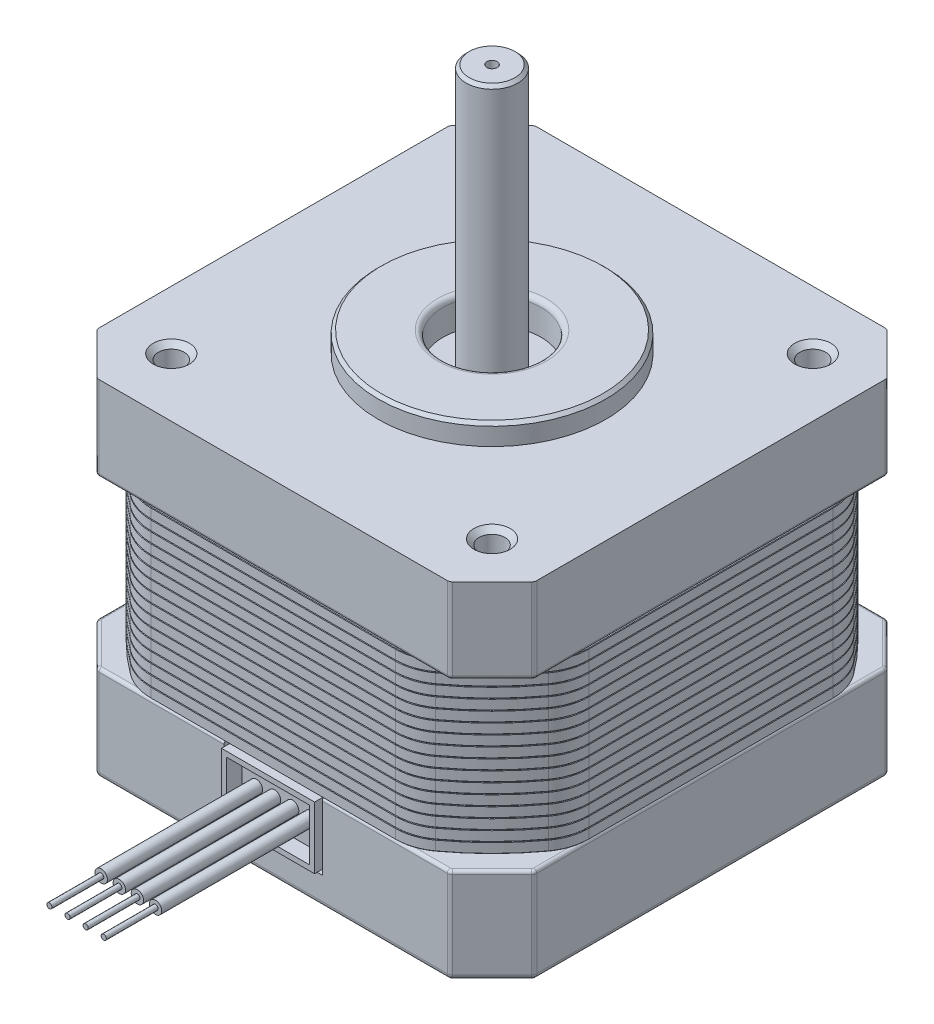
SolidWorks part; units mm, degrees
note: The reader was unsure of these and kept them because the rebuilt part matched: shared geometry of "Эскиз1<3>", "Эскиз12<2>".
ref_plane "Спереди" through (0, 0, 0) normal (0, 0, 1) x (1, 0, 0)
ref_plane "Сверху" through (0, 0, 0) normal (0, 1, 0) x (1, 0, 0)
ref_plane "Справа" through (0, 0, 0) normal (1, 0, 0) x (0, 0, -1)
sketch "Эскиз1" plane through (0, 0, 0) normal (0, 1, 0) x (1, 0, 0)
  line L0 (-21.15, 17.0338) -> (-17.0338, 21.15)
  line L1 (-21.15, 21.15) -> (21.15, 21.15)
  line L2 (-21.15, 21.15) -> (-21.15, -21.15)
  line L3 (-21.15, -21.15) -> (21.15, -21.15)
  line L4 (21.15, 21.15) -> (21.15, -21.15)
  line L5 (-21.15, 21.15) -> (21.15, -21.15) construction
  line L6 (-21.15, -21.15) -> (21.15, 21.15) construction
  line L7 (-17.0338, 21.15) -> (17.0338, 21.15)
  line L8 (17.0338, 21.15) -> (21.15, 17.0338)
  line L9 (21.15, 17.0338) -> (21.15, -17.0338)
  line L10 (21.15, -17.0338) -> (17.0338, -21.15)
  line L11 (17.0338, -21.15) -> (-17.0338, -21.15)
  line L12 (-17.0338, -21.15) -> (-21.15, -17.0338)
  point P0 (0, 0)
  dimension "D1" = 42.3
  dimension "D2" = 54
extrude "Бобышка-Вытянуть1" add sketch "Эскиз1" along normal blind 9.2 contours L12 L3 L10 L4 L8 L1 L0 L2
extrude "Бобышка-Вытянуть2" add sketch "Эскиз1<3>" against normal blind 8.2 from offset 33.4 separate body contours L12 L3 L10 L4 L8 L1 L0 L2
sketch "Эскиз1<3>" plane through (0, 0, 0) normal (0, 1, 0) x (1, 0, 0) same geometry as "Эскиз1"
sketch "Эскиз2" plane through (0, 9.2, 0) normal (0, 1, 0) x (1, 0, 0)
  line L16 (-21.15, -17.0338) -> (-17.0338, -21.15)
  line L17 (-17.0338, -21.15) -> (17.0338, -21.15)
  line L18 (17.0338, -21.15) -> (21.15, -17.0338)
  line L19 (21.15, -17.0338) -> (21.15, 17.0338)
  line L20 (21.15, 17.0338) -> (17.0338, 21.15)
  line L21 (17.0338, 21.15) -> (-17.0338, 21.15)
  line L22 (-17.0338, 21.15) -> (-21.15, 17.0338)
  line L23 (-21.15, 17.0338) -> (-21.15, -17.0338)
  line L25 (-11.7974, -21.15) -> (11.7974, -21.15)
  line L27 (21.15, -11.7974) -> (21.15, 11.7974)
  line L29 (11.7974, 21.15) -> (-11.7974, 21.15)
  line L31 (-21.15, 11.7974) -> (-21.15, -11.7974)
  arc A0 (-20.1875, -14.7467) -> (-14.7467, -20.1875) centre (0, 0) ccw
  arc A1 (-14.7467, 20.1875) -> (-20.1875, 14.7467) centre (0, 0) ccw
  arc A2 (20.1875, 14.7467) -> (14.7467, 20.1875) centre (0, 0) ccw
  arc A3 (14.7467, -20.1875) -> (20.1875, -14.7467) centre (0, 0) ccw
  arc A4 (14.7467, 20.1875) -> (11.7974, 21.15) centre (11.7974, 16.15) ccw
  arc A5 (21.15, 11.7974) -> (20.1875, 14.7467) centre (16.15, 11.7974) ccw
  arc A6 (20.1875, -14.7467) -> (21.15, -11.7974) centre (16.15, -11.7974) ccw
  arc A7 (11.7974, -21.15) -> (14.7467, -20.1875) centre (11.7974, -16.15) ccw
  arc A8 (-14.7467, -20.1875) -> (-11.7974, -21.15) centre (-11.7974, -16.15) ccw
  arc A9 (-20.1875, -14.7467) -> (-21.15, -11.7974) centre (-16.15, -11.7974) cw
  arc A10 (-20.1875, 14.7467) -> (-21.15, 11.7974) centre (-16.15, 11.7974) ccw
  arc A11 (-11.7974, 21.15) -> (-14.7467, 20.1875) centre (-11.7974, 16.15) ccw
  point P22 (21.15, 13.3296)
  point P27 (13.3296, -21.15)
  point P36 (-13.3296, 21.15)
  dimension "D1" = 50
  dimension "D3" = 5
  dimension "D2" = 0
extrude "Бобышка-Вытянуть3" add sketch "Эскиз2" along normal blind 1 separate body
pattern_linear "Линейный массив1" count 16 spacing 1 along (0, 1, 0) of bodies 105
sketch "Эскиз3" plane through (0, 0, 0) normal (0, -1, 0) x (1, 0, 0)
  circle A0 centre (0, 0) radius 4.75
  dimension "D1" = 9.5
extrude "Вырез-Вытянуть1" cut sketch "Эскиз3" against normal blind 3
sketch "Эскиз4" plane through (0, 3, 0) normal (0, -1, 0) x (1, 0, 0)
  circle A0 centre (0, 0) radius 2.5
  circle A1 centre (0, 0) radius 4.75
  dimension "D1" = 5
extrude "Вырез-Вытянуть2" cut sketch "Эскиз4" against normal blind 0.5
sketch "Эскиз5" plane through (0, 3, 0) normal (0, -1, 0) x (1, 0, 0)
  circle A0 centre (0, 0) radius 0.5
  dimension "D1" = 1
extrude "Вырез-Вытянуть3" cut sketch "Эскиз5" against normal blind 0.5
chamfer "Фаска1" distance 0.3 angle 45 1 edges at (0, 3, -2.5)
fillet "Скругление1" radius 0.5 17 edges at (0, 0, 21.15) (19.0919, 0, 19.0919) (21.15, 0, 0) (19.0919, 0, -19.0919) (0, 0, -21.15) (-19.0919, 0, -19.0919) (-21.15, 0, 0) (-19.0919, 0, 19.0919) (0, 0, -4.75) (21.15, 4.6, 17.0338) (17.0338, 4.6, 21.15) (-17.0338, 4.6, 21.15) (-21.15, 4.6, 17.0338) (-21.15, 4.6, -17.0338) (-17.0338, 4.6, -21.15) (17.0338, 4.6, -21.15) (21.15, 4.6, -17.0338)
fillet "Скругление2" radius 0.5 8 edges at (21.15, 29.3, 17.0338) (17.0338, 29.3, 21.15) (-17.0338, 29.3, 21.15) (-21.15, 29.3, 17.0338) (-21.15, 29.3, -17.0338) (-17.0338, 29.3, -21.15) (17.0338, 29.3, -21.15) (21.15, 29.3, -17.0338)
sketch "Эскиз6" plane through (0, 33.4, 0) normal (0, 1, 0) x (1, 0, 0)
  circle A0 centre (0, 0) radius 11
  circle A1 centre (0, 0) radius 4.75
  dimension "D1" = 22
  dimension "D2" = 9.5
extrude "Бобышка-Вытянуть4" add sketch "Эскиз6" along normal blind 2
sketch "Эскиз7" plane through (0, 33.4, 0) normal (0, 1, 0) x (1, 0, 0)
  circle A2 centre (0, 0) radius 4.75
  circle A3 centre (0, 0) radius 4.75
  dimension "D1" = 0
extrude "Вырез-Вытянуть4" cut sketch "Эскиз7" against normal blind 1
chamfer "Фаска2" distance 0.3 angle 45 1 edges at (0, 35.4, 11)
fillet "Скругление3" radius 0.5 1 edges at (0, 35.4, 4.75)
sketch "Эскиз8" plane through (0, 32.4, 0) normal (0, 1, 0) x (1, 0, 0)
  circle A0 centre (0, 0) radius 2.5
  dimension "D1" = 5
extrude "Бобышка-Вытянуть5" add sketch "Эскиз8" along normal blind 25.2
chamfer "Фаска4" distance 0.3 angle 45 1 edges at (0, 57.6, 2.5)
sketch "Эскиз9" plane through (0, 57.6, 0) normal (0, 1, 0) x (1, 0, 0)
  circle A0 centre (0, 0) radius 0.5
  dimension "D1" = 1
extrude "Вырез-Вытянуть5" cut sketch "Эскиз9" against normal blind 1
sketch "Эскиз10" plane through (0, 0, 21.15) normal (0, 0, 1) x (1, 0, 0)
  line L0 (0, 0) -> (0, 9.2) construction
  line L1 (-11.7974, 9.2) -> (11.7974, 9.2) construction
  line L2 (-16.8267, 9.2) -> (16.8267, 9.2) construction
  line L3 (-4.75, 2.7) -> (4.75, 2.7)
  line L4 (-4.75, 2.7) -> (-4.75, 9.2)
  line L5 (-4.75, 9.2) -> (4.75, 9.2)
  line L6 (4.75, 2.7) -> (4.75, 9.2)
  line L7 (-4.75, 2.7) -> (4.75, 9.2) construction
  line L8 (-4.75, 9.2) -> (4.75, 2.7) construction
  point P5 (0, 5.95)
  dimension "D1" = 9.5
  dimension "D2" = 6.5
extrude "Вырез-Вытянуть6" cut sketch "Эскиз10" against normal blind 1
sketch "Эскиз11" plane through (0, 0, 20.15) normal (0, 0, 1) x (1, 0, 0)
  line L8 (4.5, 2.95) -> (4.5, 8.95)
  line L9 (4.5, 8.95) -> (-4.5, 8.95)
  line L10 (-4.5, 8.95) -> (-4.5, 2.95)
  line L11 (-4.5, 2.95) -> (4.5, 2.95)
  line L12 (4.5, 2.95) -> (4.5, 8.95)
  line L13 (4.5, 8.95) -> (-4.5, 8.95)
  line L14 (-4.5, 8.95) -> (-4.5, 2.95)
  line L15 (-4.5, 2.95) -> (4.5, 2.95)
  line L20 (4, 3.45) -> (4, 8.45)
  line L21 (4, 8.45) -> (-4, 8.45)
  line L22 (-4, 8.45) -> (-4, 3.45)
  line L23 (-4, 3.45) -> (4, 3.45)
  line L24 (4, 3.45) -> (4, 8.45)
  line L25 (4, 8.45) -> (-4, 8.45)
  line L26 (-4, 8.45) -> (-4, 3.45)
  line L27 (-4, 3.45) -> (4, 3.45)
  dimension "D1" = 0.25
  dimension "D2" = 0.75
extrude "Бобышка-Вытянуть6" add sketch "Эскиз11" along normal blind 1.5 separate body
sketch "Эскиз12" plane through (0, 0, 20.15) normal (0, 0, 1) x (1, 0, 0)
  line L0 (-4, 5.95) -> (4, 5.95) construction
  line L1 (-4, 8.45) -> (-4, 3.45) construction
  line L2 (4, 3.45) -> (4, 8.45) construction
  line L3 (-2.625, 5.95) -> (-2.625, 4.3362) construction
  line L4 (-2.625, 4.3362) -> (-0.875, 4.3362) construction
  line L5 (-0.875, 4.3362) -> (-0.875, 5.95) construction
  line L6 (-0.875, 5.95) -> (-0.875, 4.3362) construction
  line L7 (-0.875, 4.3362) -> (0.875, 4.3362) construction
  line L8 (0.875, 4.3362) -> (0.875, 5.95) construction
  line L9 (0.875, 5.95) -> (0.875, 4.3362) construction
  line L10 (0.875, 4.3362) -> (2.625, 4.3362) construction
  line L11 (2.625, 4.3362) -> (2.625, 5.95) construction
  line L12 (0, 5.95) -> (0, 4.3362) construction
  circle A0 centre (-2.625, 5.95) radius 0.6
  circle A1 centre (-0.875, 5.95) radius 0.6
  circle A2 centre (0.875, 5.95) radius 0.6
  circle A3 centre (2.625, 5.95) radius 0.6
  circle A4 centre (-2.625, 5.95) radius 0.25
  circle A5 centre (-0.875, 5.95) radius 0.25
  circle A6 centre (0.875, 5.95) radius 0.25
  circle A7 centre (2.625, 5.95) radius 0.25
  dimension "D1" = 1.2
  dimension "D2" = 0.5
  dimension "D3" = 1.75
extrude "Бобышка-Вытянуть7" add sketch "Эскиз12" along normal blind 15 separate body
extrude "Бобышка-Вытянуть8" add sketch "Эскиз12<2>" along normal blind 20 separate body contours A4 | A5 | A6 | A7
sketch "Эскиз12<2>" plane through (0, 0, 20.15) normal (0, 0, 1) x (1, 0, 0) same geometry as "Эскиз12"
chamfer "Фаска19" distance 0.05 angle 45 32 edges at (-17.6777, 25.2, -17.6777) (-20.9033, 25.2, -13.3486) (-13.3486, 25.2, -20.9033) (-21.15, 25.2, 0) (0, 25.2, -21.15) (-20.9033, 25.2, 13.3486) (13.3486, 25.2, -20.9033) (-17.6777, 25.2, 17.6777) (17.6777, 25.2, -17.6777) (-13.3486, 25.2, 20.9033) (20.9033, 25.2, -13.3486) (0, 25.2, 21.15) (21.15, 25.2, 0) (13.3486, 25.2, 20.9033) (20.9033, 25.2, 13.3486) (17.6777, 25.2, 17.6777) (-17.6777, 24.2, -17.6777) (-20.9033, 24.2, -13.3486) (-13.3486, 24.2, -20.9033) (-21.15, 24.2, 0) (0, 24.2, -21.15) (-20.9033, 24.2, 13.3486) (13.3486, 24.2, -20.9033) (-17.6777, 24.2, 17.6777) (17.6777, 24.2, -17.6777) (-13.3486, 24.2, 20.9033) (20.9033, 24.2, -13.3486) (0, 24.2, 21.15) (21.15, 24.2, 0) (13.3486, 24.2, 20.9033) (20.9033, 24.2, 13.3486) (17.6777, 24.2, 17.6777)
chamfer "Фаска20" distance 0.05 angle 45 32 edges at (-17.6777, 24.2, -17.6777) (-20.9033, 24.2, -13.3486) (-13.3486, 24.2, -20.9033) (-21.15, 24.2, 0) (0, 24.2, -21.15) (-20.9033, 24.2, 13.3486) (13.3486, 24.2, -20.9033) (-17.6777, 24.2, 17.6777) (17.6777, 24.2, -17.6777) (-13.3486, 24.2, 20.9033) (20.9033, 24.2, -13.3486) (0, 24.2, 21.15) (21.15, 24.2, 0) (13.3486, 24.2, 20.9033) (20.9033, 24.2, 13.3486) (17.6777, 24.2, 17.6777) (-17.6777, 23.2, -17.6777) (-20.9033, 23.2, -13.3486) (-13.3486, 23.2, -20.9033) (-21.15, 23.2, 0) (0, 23.2, -21.15) (-20.9033, 23.2, 13.3486) (13.3486, 23.2, -20.9033) (-17.6777, 23.2, 17.6777) (17.6777, 23.2, -17.6777) (-13.3486, 23.2, 20.9033) (20.9033, 23.2, -13.3486) (0, 23.2, 21.15) (21.15, 23.2, 0) (13.3486, 23.2, 20.9033) (20.9033, 23.2, 13.3486) (17.6777, 23.2, 17.6777)
chamfer "Фаска21" distance 0.05 angle 45 32 edges at (-17.6777, 23.2, -17.6777) (-20.9033, 23.2, -13.3486) (-13.3486, 23.2, -20.9033) (-21.15, 23.2, 0) (0, 23.2, -21.15) (-20.9033, 23.2, 13.3486) (13.3486, 23.2, -20.9033) (-17.6777, 23.2, 17.6777) (17.6777, 23.2, -17.6777) (-13.3486, 23.2, 20.9033) (20.9033, 23.2, -13.3486) (0, 23.2, 21.15) (21.15, 23.2, 0) (13.3486, 23.2, 20.9033) (20.9033, 23.2, 13.3486) (17.6777, 23.2, 17.6777) (-17.6777, 22.2, -17.6777) (-20.9033, 22.2, -13.3486) (-13.3486, 22.2, -20.9033) (-21.15, 22.2, 0) (0, 22.2, -21.15) (-20.9033, 22.2, 13.3486) (13.3486, 22.2, -20.9033) (-17.6777, 22.2, 17.6777) (17.6777, 22.2, -17.6777) (-13.3486, 22.2, 20.9033) (20.9033, 22.2, -13.3486) (0, 22.2, 21.15) (21.15, 22.2, 0) (13.3486, 22.2, 20.9033) (20.9033, 22.2, 13.3486) (17.6777, 22.2, 17.6777)
chamfer "Фаска22" distance 0.05 angle 45 32 edges at (-17.6777, 22.2, -17.6777) (-20.9033, 22.2, -13.3486) (-13.3486, 22.2, -20.9033) (-21.15, 22.2, 0) (0, 22.2, -21.15) (-20.9033, 22.2, 13.3486) (13.3486, 22.2, -20.9033) (-17.6777, 22.2, 17.6777) (17.6777, 22.2, -17.6777) (-13.3486, 22.2, 20.9033) (20.9033, 22.2, -13.3486) (0, 22.2, 21.15) (21.15, 22.2, 0) (13.3486, 22.2, 20.9033) (20.9033, 22.2, 13.3486) (17.6777, 22.2, 17.6777) (-17.6777, 21.2, -17.6777) (-20.9033, 21.2, -13.3486) (-13.3486, 21.2, -20.9033) (-21.15, 21.2, 0) (0, 21.2, -21.15) (-20.9033, 21.2, 13.3486) (13.3486, 21.2, -20.9033) (-17.6777, 21.2, 17.6777) (17.6777, 21.2, -17.6777) (-13.3486, 21.2, 20.9033) (20.9033, 21.2, -13.3486) (0, 21.2, 21.15) (21.15, 21.2, 0) (13.3486, 21.2, 20.9033) (20.9033, 21.2, 13.3486) (17.6777, 21.2, 17.6777)
chamfer "Фаска23" distance 0.05 angle 45 32 edges at (-17.6777, 21.2, -17.6777) (-20.9033, 21.2, -13.3486) (-13.3486, 21.2, -20.9033) (-21.15, 21.2, 0) (0, 21.2, -21.15) (-20.9033, 21.2, 13.3486) (13.3486, 21.2, -20.9033) (-17.6777, 21.2, 17.6777) (17.6777, 21.2, -17.6777) (-13.3486, 21.2, 20.9033) (20.9033, 21.2, -13.3486) (0, 21.2, 21.15) (21.15, 21.2, 0) (13.3486, 21.2, 20.9033) (20.9033, 21.2, 13.3486) (17.6777, 21.2, 17.6777) (-17.6777, 20.2, -17.6777) (-20.9033, 20.2, -13.3486) (-13.3486, 20.2, -20.9033) (-21.15, 20.2, 0) (0, 20.2, -21.15) (-20.9033, 20.2, 13.3486) (13.3486, 20.2, -20.9033) (-17.6777, 20.2, 17.6777) (17.6777, 20.2, -17.6777) (-13.3486, 20.2, 20.9033) (20.9033, 20.2, -13.3486) (0, 20.2, 21.15) (21.15, 20.2, 0) (13.3486, 20.2, 20.9033) (20.9033, 20.2, 13.3486) (17.6777, 20.2, 17.6777)
chamfer "Фаска24" distance 0.05 angle 45 32 edges at (-17.6777, 20.2, -17.6777) (-20.9033, 20.2, -13.3486) (-13.3486, 20.2, -20.9033) (-21.15, 20.2, 0) (0, 20.2, -21.15) (-20.9033, 20.2, 13.3486) (13.3486, 20.2, -20.9033) (-17.6777, 20.2, 17.6777) (17.6777, 20.2, -17.6777) (-13.3486, 20.2, 20.9033) (20.9033, 20.2, -13.3486) (0, 20.2, 21.15) (21.15, 20.2, 0) (13.3486, 20.2, 20.9033) (20.9033, 20.2, 13.3486) (17.6777, 20.2, 17.6777) (-17.6777, 19.2, -17.6777) (-20.9033, 19.2, -13.3486) (-13.3486, 19.2, -20.9033) (-21.15, 19.2, 0) (0, 19.2, -21.15) (-20.9033, 19.2, 13.3486) (13.3486, 19.2, -20.9033) (-17.6777, 19.2, 17.6777) (17.6777, 19.2, -17.6777) (-13.3486, 19.2, 20.9033) (20.9033, 19.2, -13.3486) (0, 19.2, 21.15) (21.15, 19.2, 0) (13.3486, 19.2, 20.9033) (20.9033, 19.2, 13.3486) (17.6777, 19.2, 17.6777)
chamfer "Фаска25" distance 0.05 angle 45 32 edges at (-17.6777, 19.2, -17.6777) (-20.9033, 19.2, -13.3486) (-13.3486, 19.2, -20.9033) (-21.15, 19.2, 0) (0, 19.2, -21.15) (-20.9033, 19.2, 13.3486) (13.3486, 19.2, -20.9033) (-17.6777, 19.2, 17.6777) (17.6777, 19.2, -17.6777) (-13.3486, 19.2, 20.9033) (20.9033, 19.2, -13.3486) (0, 19.2, 21.15) (21.15, 19.2, 0) (13.3486, 19.2, 20.9033) (20.9033, 19.2, 13.3486) (17.6777, 19.2, 17.6777) (-17.6777, 18.2, -17.6777) (-20.9033, 18.2, -13.3486) (-13.3486, 18.2, -20.9033) (-21.15, 18.2, 0) (0, 18.2, -21.15) (-20.9033, 18.2, 13.3486) (13.3486, 18.2, -20.9033) (-17.6777, 18.2, 17.6777) (17.6777, 18.2, -17.6777) (-13.3486, 18.2, 20.9033) (20.9033, 18.2, -13.3486) (0, 18.2, 21.15) (21.15, 18.2, 0) (13.3486, 18.2, 20.9033) (20.9033, 18.2, 13.3486) (17.6777, 18.2, 17.6777)
chamfer "Фаска26" distance 0.05 angle 45 32 edges at (-17.6777, 18.2, -17.6777) (-20.9033, 18.2, -13.3486) (-13.3486, 18.2, -20.9033) (-21.15, 18.2, 0) (0, 18.2, -21.15) (-20.9033, 18.2, 13.3486) (13.3486, 18.2, -20.9033) (-17.6777, 18.2, 17.6777) (17.6777, 18.2, -17.6777) (-13.3486, 18.2, 20.9033) (20.9033, 18.2, -13.3486) (0, 18.2, 21.15) (21.15, 18.2, 0) (13.3486, 18.2, 20.9033) (20.9033, 18.2, 13.3486) (17.6777, 18.2, 17.6777) (-17.6777, 17.2, -17.6777) (-20.9033, 17.2, -13.3486) (-13.3486, 17.2, -20.9033) (-21.15, 17.2, 0) (0, 17.2, -21.15) (-20.9033, 17.2, 13.3486) (13.3486, 17.2, -20.9033) (-17.6777, 17.2, 17.6777) (17.6777, 17.2, -17.6777) (-13.3486, 17.2, 20.9033) (20.9033, 17.2, -13.3486) (0, 17.2, 21.15) (21.15, 17.2, 0) (13.3486, 17.2, 20.9033) (20.9033, 17.2, 13.3486) (17.6777, 17.2, 17.6777)
chamfer "Фаска27" distance 0.05 angle 45 32 edges at (-17.6777, 17.2, -17.6777) (-20.9033, 17.2, -13.3486) (-13.3486, 17.2, -20.9033) (-21.15, 17.2, 0) (0, 17.2, -21.15) (-20.9033, 17.2, 13.3486) (13.3486, 17.2, -20.9033) (-17.6777, 17.2, 17.6777) (17.6777, 17.2, -17.6777) (-13.3486, 17.2, 20.9033) (20.9033, 17.2, -13.3486) (0, 17.2, 21.15) (21.15, 17.2, 0) (13.3486, 17.2, 20.9033) (20.9033, 17.2, 13.3486) (17.6777, 17.2, 17.6777) (-17.6777, 16.2, -17.6777) (-20.9033, 16.2, -13.3486) (-13.3486, 16.2, -20.9033) (-21.15, 16.2, 0) (0, 16.2, -21.15) (-20.9033, 16.2, 13.3486) (13.3486, 16.2, -20.9033) (-17.6777, 16.2, 17.6777) (17.6777, 16.2, -17.6777) (-13.3486, 16.2, 20.9033) (20.9033, 16.2, -13.3486) (0, 16.2, 21.15) (21.15, 16.2, 0) (13.3486, 16.2, 20.9033) (20.9033, 16.2, 13.3486) (17.6777, 16.2, 17.6777)
chamfer "Фаска28" distance 0.05 angle 45 32 edges at (-17.6777, 16.2, -17.6777) (-20.9033, 16.2, -13.3486) (-13.3486, 16.2, -20.9033) (-21.15, 16.2, 0) (0, 16.2, -21.15) (-20.9033, 16.2, 13.3486) (13.3486, 16.2, -20.9033) (-17.6777, 16.2, 17.6777) (17.6777, 16.2, -17.6777) (-13.3486, 16.2, 20.9033) (20.9033, 16.2, -13.3486) (0, 16.2, 21.15) (21.15, 16.2, 0) (13.3486, 16.2, 20.9033) (20.9033, 16.2, 13.3486) (17.6777, 16.2, 17.6777) (-17.6777, 15.2, -17.6777) (-20.9033, 15.2, -13.3486) (-13.3486, 15.2, -20.9033) (-21.15, 15.2, 0) (0, 15.2, -21.15) (-20.9033, 15.2, 13.3486) (13.3486, 15.2, -20.9033) (-17.6777, 15.2, 17.6777) (17.6777, 15.2, -17.6777) (-13.3486, 15.2, 20.9033) (20.9033, 15.2, -13.3486) (0, 15.2, 21.15) (21.15, 15.2, 0) (13.3486, 15.2, 20.9033) (20.9033, 15.2, 13.3486) (17.6777, 15.2, 17.6777)
chamfer "Фаска29" distance 0.05 angle 45 32 edges at (-17.6777, 15.2, -17.6777) (-20.9033, 15.2, -13.3486) (-13.3486, 15.2, -20.9033) (-21.15, 15.2, 0) (0, 15.2, -21.15) (-20.9033, 15.2, 13.3486) (13.3486, 15.2, -20.9033) (-17.6777, 15.2, 17.6777) (17.6777, 15.2, -17.6777) (-13.3486, 15.2, 20.9033) (20.9033, 15.2, -13.3486) (0, 15.2, 21.15) (21.15, 15.2, 0) (13.3486, 15.2, 20.9033) (20.9033, 15.2, 13.3486) (17.6777, 15.2, 17.6777) (-17.6777, 14.2, -17.6777) (-20.9033, 14.2, -13.3486) (-13.3486, 14.2, -20.9033) (-21.15, 14.2, 0) (0, 14.2, -21.15) (-20.9033, 14.2, 13.3486) (13.3486, 14.2, -20.9033) (-17.6777, 14.2, 17.6777) (17.6777, 14.2, -17.6777) (-13.3486, 14.2, 20.9033) (20.9033, 14.2, -13.3486) (0, 14.2, 21.15) (21.15, 14.2, 0) (13.3486, 14.2, 20.9033) (20.9033, 14.2, 13.3486) (17.6777, 14.2, 17.6777)
chamfer "Фаска30" distance 0.05 angle 45 32 edges at (-17.6777, 14.2, -17.6777) (-20.9033, 14.2, -13.3486) (-13.3486, 14.2, -20.9033) (-21.15, 14.2, 0) (0, 14.2, -21.15) (-20.9033, 14.2, 13.3486) (13.3486, 14.2, -20.9033) (-17.6777, 14.2, 17.6777) (17.6777, 14.2, -17.6777) (-13.3486, 14.2, 20.9033) (20.9033, 14.2, -13.3486) (0, 14.2, 21.15) (21.15, 14.2, 0) (13.3486, 14.2, 20.9033) (20.9033, 14.2, 13.3486) (17.6777, 14.2, 17.6777) (-17.6777, 13.2, -17.6777) (-20.9033, 13.2, -13.3486) (-13.3486, 13.2, -20.9033) (-21.15, 13.2, 0) (0, 13.2, -21.15) (-20.9033, 13.2, 13.3486) (13.3486, 13.2, -20.9033) (-17.6777, 13.2, 17.6777) (17.6777, 13.2, -17.6777) (-13.3486, 13.2, 20.9033) (20.9033, 13.2, -13.3486) (0, 13.2, 21.15) (21.15, 13.2, 0) (13.3486, 13.2, 20.9033) (20.9033, 13.2, 13.3486) (17.6777, 13.2, 17.6777)
chamfer "Фаска31" distance 0.05 angle 45 32 edges at (-17.6777, 13.2, -17.6777) (-20.9033, 13.2, -13.3486) (-13.3486, 13.2, -20.9033) (-21.15, 13.2, 0) (0, 13.2, -21.15) (-20.9033, 13.2, 13.3486) (13.3486, 13.2, -20.9033) (-17.6777, 13.2, 17.6777) (17.6777, 13.2, -17.6777) (-13.3486, 13.2, 20.9033) (20.9033, 13.2, -13.3486) (0, 13.2, 21.15) (21.15, 13.2, 0) (13.3486, 13.2, 20.9033) (20.9033, 13.2, 13.3486) (17.6777, 13.2, 17.6777) (-17.6777, 12.2, -17.6777) (-20.9033, 12.2, -13.3486) (-13.3486, 12.2, -20.9033) (-21.15, 12.2, 0) (0, 12.2, -21.15) (-20.9033, 12.2, 13.3486) (13.3486, 12.2, -20.9033) (-17.6777, 12.2, 17.6777) (17.6777, 12.2, -17.6777) (-13.3486, 12.2, 20.9033) (20.9033, 12.2, -13.3486) (0, 12.2, 21.15) (21.15, 12.2, 0) (13.3486, 12.2, 20.9033) (20.9033, 12.2, 13.3486) (17.6777, 12.2, 17.6777)
chamfer "Фаска32" distance 0.05 angle 45 32 edges at (-17.6777, 12.2, -17.6777) (-20.9033, 12.2, -13.3486) (-13.3486, 12.2, -20.9033) (-21.15, 12.2, 0) (0, 12.2, -21.15) (-20.9033, 12.2, 13.3486) (13.3486, 12.2, -20.9033) (-17.6777, 12.2, 17.6777) (17.6777, 12.2, -17.6777) (-13.3486, 12.2, 20.9033) (20.9033, 12.2, -13.3486) (0, 12.2, 21.15) (21.15, 12.2, 0) (13.3486, 12.2, 20.9033) (20.9033, 12.2, 13.3486) (17.6777, 12.2, 17.6777) (-17.6777, 11.2, -17.6777) (-20.9033, 11.2, -13.3486) (-13.3486, 11.2, -20.9033) (-21.15, 11.2, 0) (0, 11.2, -21.15) (-20.9033, 11.2, 13.3486) (13.3486, 11.2, -20.9033) (-17.6777, 11.2, 17.6777) (17.6777, 11.2, -17.6777) (-13.3486, 11.2, 20.9033) (20.9033, 11.2, -13.3486) (0, 11.2, 21.15) (21.15, 11.2, 0) (13.3486, 11.2, 20.9033) (20.9033, 11.2, 13.3486) (17.6777, 11.2, 17.6777)
chamfer "Фаска33" distance 0.05 angle 45 32 edges at (-17.6777, 11.2, -17.6777) (-20.9033, 11.2, -13.3486) (-13.3486, 11.2, -20.9033) (-21.15, 11.2, 0) (0, 11.2, -21.15) (-20.9033, 11.2, 13.3486) (13.3486, 11.2, -20.9033) (-17.6777, 11.2, 17.6777) (17.6777, 11.2, -17.6777) (-13.3486, 11.2, 20.9033) (20.9033, 11.2, -13.3486) (0, 11.2, 21.15) (21.15, 11.2, 0) (13.3486, 11.2, 20.9033) (20.9033, 11.2, 13.3486) (17.6777, 11.2, 17.6777) (-17.6777, 10.2, -17.6777) (-20.9033, 10.2, -13.3486) (-13.3486, 10.2, -20.9033) (-21.15, 10.2, 0) (0, 10.2, -21.15) (-20.9033, 10.2, 13.3486) (13.3486, 10.2, -20.9033) (-17.6777, 10.2, 17.6777) (17.6777, 10.2, -17.6777) (-13.3486, 10.2, 20.9033) (20.9033, 10.2, -13.3486) (0, 10.2, 21.15) (21.15, 10.2, 0) (13.3486, 10.2, 20.9033) (20.9033, 10.2, 13.3486) (17.6777, 10.2, 17.6777)
chamfer "Фаска34" distance 0.05 angle 45 32 edges at (-17.6777, 10.2, -17.6777) (-20.9033, 10.2, -13.3486) (-13.3486, 10.2, -20.9033) (-21.15, 10.2, 0) (0, 10.2, -21.15) (-20.9033, 10.2, 13.3486) (13.3486, 10.2, -20.9033) (-17.6777, 10.2, 17.6777) (17.6777, 10.2, -17.6777) (-13.3486, 10.2, 20.9033) (20.9033, 10.2, -13.3486) (0, 10.2, 21.15) (21.15, 10.2, 0) (13.3486, 10.2, 20.9033) (20.9033, 10.2, 13.3486) (17.6777, 10.2, 17.6777) (-17.6777, 9.2, -17.6777) (-20.9033, 9.2, -13.3486) (-13.3486, 9.2, -20.9033) (-21.15, 9.2, 0) (0, 9.2, -21.15) (-20.9033, 9.2, 13.3486) (13.3486, 9.2, -20.9033) (-17.6777, 9.2, 17.6777) (17.6777, 9.2, -17.6777) (-13.3486, 9.2, 20.9033) (20.9033, 9.2, -13.3486) (0, 9.2, 21.15) (21.15, 9.2, 0) (13.3486, 9.2, 20.9033) (20.9033, 9.2, 13.3486) (17.6777, 9.2, 17.6777)
sketch "Эскиз16" plane through (0, 33.4, 0) normal (0, 1, 0) x (1, 0, 0)
  line L1 (-15.5, 15.5) -> (15.5, 15.5) construction
  line L2 (-15.5, 15.5) -> (-15.5, -15.5) construction
  line L3 (-15.5, -15.5) -> (15.5, -15.5) construction
  line L4 (15.5, 15.5) -> (15.5, -15.5) construction
  line L5 (-15.5, 15.5) -> (15.5, -15.5) construction
  line L6 (-15.5, -15.5) -> (15.5, 15.5) construction
  circle A0 centre (-15.5, 15.5) radius 1.25
  circle A1 centre (15.5, 15.5) radius 1.25
  circle A2 centre (15.5, -15.5) radius 1.25
  circle A3 centre (-15.5, -15.5) radius 1.25
  point P0 (0, 0)
  dimension "D1" = 2.5
  dimension "D2" = 31
extrude "Вырез-Вытянуть9" cut sketch "Эскиз16" against normal blind 7
chamfer "Фаска35" distance 0.5 angle 45 4 edges at (-15.5, 33.4, 16.75) (15.5, 33.4, 16.75) (15.5, 33.4, -14.25) (-15.5, 33.4, -14.25)
fillet "Скругление4" radius 0.3 17 edges at (-10.7883, 9.2, 21.15) (-17.018, 9.2, 21.1119) (-19.0919, 9.2, 19.0919) (-21.1119, 9.2, 17.018) (-21.15, 9.2, 0) (-21.1119, 9.2, -17.018) (-19.0919, 9.2, -19.0919) (-17.018, 9.2, -21.1119) (0, 9.2, -21.15) (17.018, 9.2, -21.1119) (19.0919, 9.2, -19.0919) (21.1119, 9.2, -17.018) (21.15, 9.2, 0) (21.1119, 9.2, 17.018) (10.7883, 9.2, 21.15) (17.018, 9.2, 21.1119) (19.0919, 9.2, 19.0919)
fillet "Скругление5" radius 0.3 16 edges at (21.1119, 25.2, 17.018) (21.15, 25.2, 0) (21.1119, 25.2, -17.018) (19.0919, 25.2, -19.0919) (17.018, 25.2, -21.1119) (0, 25.2, -21.15) (-17.018, 25.2, -21.1119) (-19.0919, 25.2, -19.0919) (-21.1119, 25.2, -17.018) (-21.15, 25.2, 0) (-21.1119, 25.2, 17.018) (-19.0919, 25.2, 19.0919) (-17.018, 25.2, 21.1119) (0, 25.2, 21.15) (17.018, 25.2, 21.1119) (19.0919, 25.2, 19.0919)
